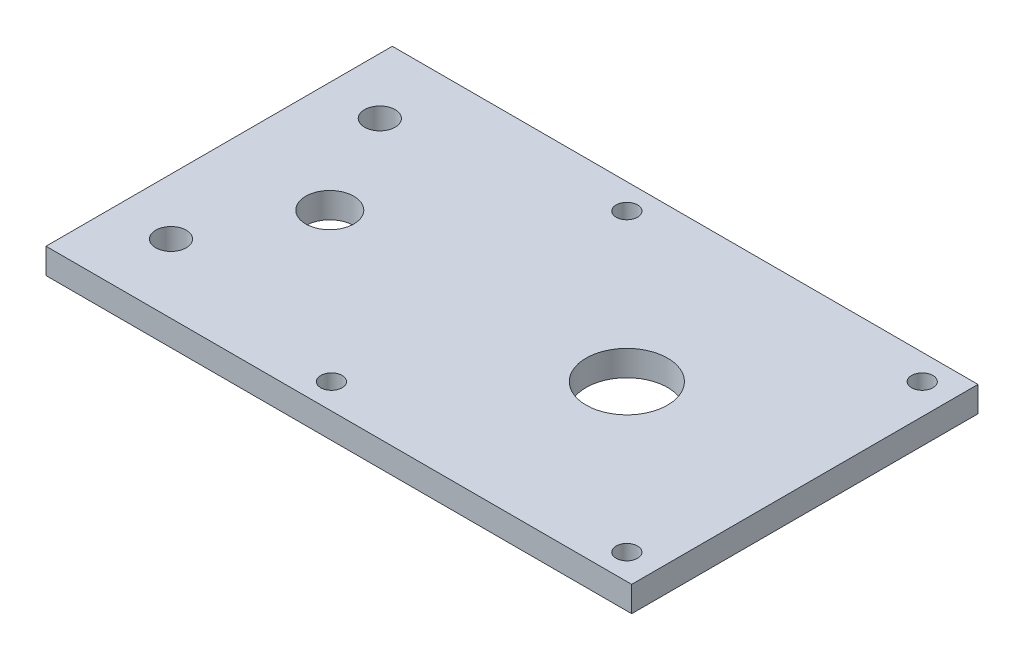
SolidWorks part; units mm, degrees
ref_plane "Front Plane" through (0, 0, 0) normal (0, 0, 1) x (1, 0, 0)
ref_plane "Top Plane" through (0, 0, 0) normal (0, 1, 0) x (1, 0, 0)
ref_plane "Right Plane" through (0, 0, 0) normal (1, 0, 0) x (0, 0, -1)
sketch "Sketch1" plane through (0, 0, 0) normal (0, 1, 0) x (1, 0, 0)
  line L0 (-57.5, 0) -> (57.5, 0) construction
  line L1 (57.5, -34) -> (-57.5, -34)
  line L2 (57.5, -34) -> (57.5, 34)
  line L3 (57.5, 34) -> (-57.5, 34)
  line L4 (-57.5, -34) -> (-57.5, 34)
  line L5 (57.5, -34) -> (-57.5, 34) construction
  line L6 (57.5, 34) -> (-57.5, -34) construction
  line L7 (22.55, 34) -> (22.55, -34) construction
  line L8 (49.455, -31.1) -> (-49.455, -31.1) construction
  line L9 (49.455, -31.1) -> (49.455, 31.1) construction
  line L10 (49.455, 31.1) -> (-49.455, 31.1) construction
  line L11 (-49.455, -31.1) -> (-49.455, 31.1) construction
  line L12 (49.455, -31.1) -> (-49.455, 31.1) construction
  line L13 (49.455, 31.1) -> (-49.455, -31.1) construction
  circle A0 centre (-6.45, 29) radius 2.1
  circle A1 centre (51.55, 29) radius 2.095
  circle A2 centre (51.55, -29) radius 2.1
  circle A3 centre (-6.45, -29) radius 2.1
  circle A4 centre (22.55, 0) radius 8
  circle A5 centre (-46.455, 20.5) radius 3
  circle A6 centre (-35.78, 0) radius 4.725
  circle A7 centre (-46.455, -20.5) radius 3
  point P0 (0, 0)
  point P6 (0, 0)
  point P13 (22.55, 0)
  point P18 (0, 0)
  point P27 (22.55, 0)
  point P34 (0, 0)
  point P35 (72.7744, -25.752)
  point P36 (0, 0)
  point P37 (0, 0)
  point P38 (-6.45, -23.6247)
  point P39 (52.5, 0)
  point P40 (-52.5, 0)
  point P41 (22.55, -34)
  point P42 (22.55, 34)
  dimension "D3" = 4.2
  dimension "D4" = 16
  dimension "D8" = 9.45
  dimension "D9" = 6
  dimension "D1" = 115
  dimension "D2" = 68
  dimension "D5" = 29
  dimension "D6" = 29
  dimension "D7" = 29
  dimension "D10" = 58.33
  dimension "D11" = 10.675
  dimension "D12" = 20.5
  dimension "D13" = 98.91
  dimension "D14" = 62.2
  dimension "D15" = 72.005
  dimension "D16" = 98.91
extrude "Boss-Extrude1" add sketch "Sketch1" along normal blind 5 contours A2 L2 A1 L3 L4 L1 A6 A5 A4 A3 A0 A7 region at (-0.0866, 0, -0.0003)
